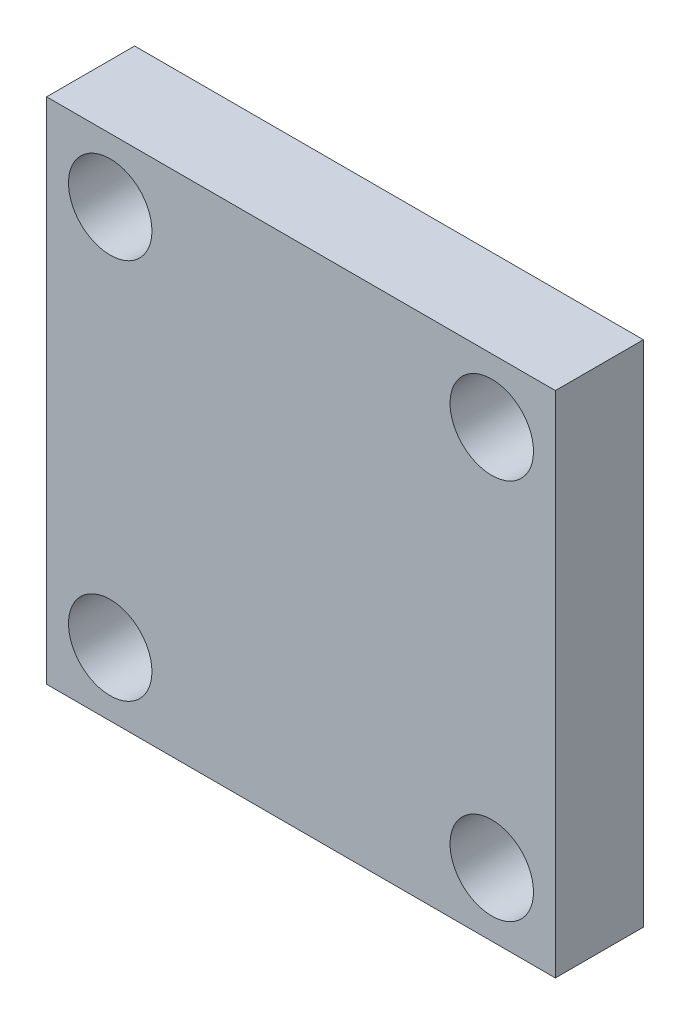
SolidWorks part; units mm, degrees
ref_plane "Front Plane" through (0, 0, 0) normal (0, 0, 1) x (1, 0, 0)
ref_plane "Top Plane" through (0, 0, 0) normal (0, 1, 0) x (1, 0, 0)
ref_plane "Right Plane" through (0, 0, 0) normal (1, 0, 0) x (0, 0, -1)
sketch "Sketch1" plane through (0, 0, 0) normal (0, 0, 1) x (1, 0, 0)
  line L0 (12.7, 25.4) -> (12.7, 0) construction
  line L1 (0, 0) -> (25.4, 0)
  line L2 (0, 0) -> (0, 25.4)
  line L3 (0, 25.4) -> (25.4, 25.4)
  line L4 (25.4, 0) -> (25.4, 25.4)
  line L5 (0, 12.7) -> (25.4, 12.7) construction
  circle A0 centre (3.175, 3.175) radius 2.0828
  circle A1 centre (3.175, 22.225) radius 2.0828
  circle A2 centre (22.225, 22.225) radius 2.0828
  circle A3 centre (22.225, 3.175) radius 2.0828
  dimension "D1" = 4.1656
  dimension "D2" = 19.05
  dimension "D3" = 19.05
  dimension "D4" = 25.4
  dimension "D5" = 25.4
  dimension "D6" = 19.05
  dimension "D7" = 19.05
extrude "Boss-Extrude1" add sketch "Sketch1" along normal blind 4.3942
